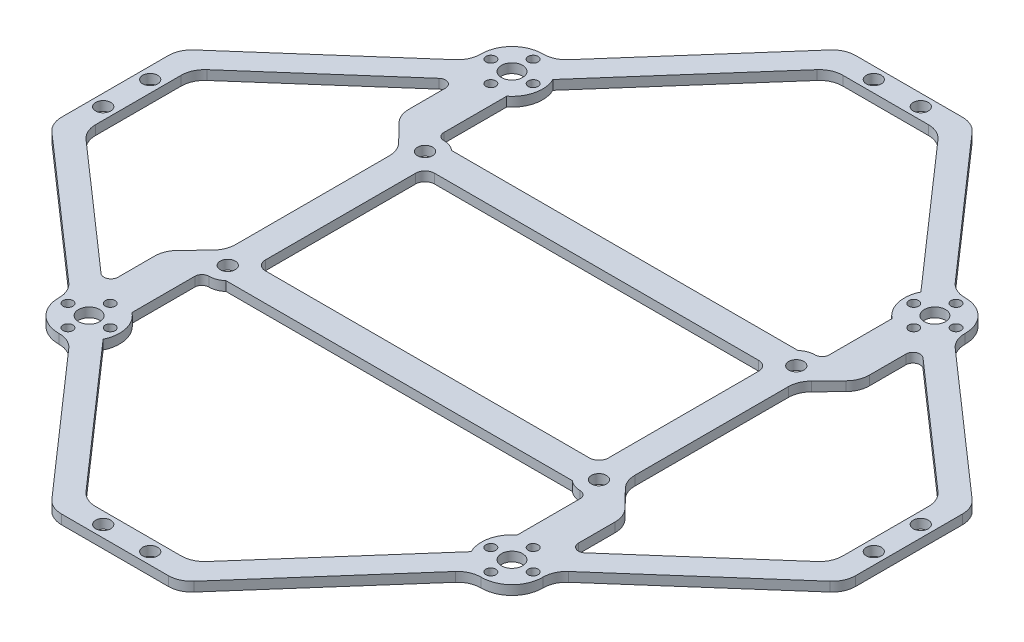
SolidWorks part; units mm, degrees
ref_plane "前视基准面" through (0, 0, 0) normal (0, 0, 1) x (1, 0, 0)
ref_plane "上视基准面" through (0, 0, 0) normal (0, 1, 0) x (1, 0, 0)
ref_plane "右视基准面" through (0, 0, 0) normal (1, 0, 0) x (0, 0, -1)
other "Configuration Table"
sketch "草图1" plane through (0, 0, 0) normal (0, 1, 0) x (1, 0, 0)
  line L0 (49, -45) -> (49, -39.8765) construction
  line L1 (-45, -45) -> (45, -45) construction
  line L2 (-45, -45) -> (-45, 45) construction
  line L3 (-45, 45) -> (45, 45) construction
  line L4 (45, -45) -> (45, 45) construction
  line L5 (-45, -45) -> (45, 45) construction
  line L6 (-45, 45) -> (45, -45) construction
  line L7 (-43.5, -25) -> (43.5, -25) construction
  line L8 (-43.5, -25) -> (-43.5, 25) construction
  line L9 (-43.5, 25) -> (43.5, 25) construction
  line L10 (43.5, -25) -> (43.5, 25) construction
  line L11 (-43.5, -25) -> (43.5, 25) construction
  line L12 (-43.5, 25) -> (43.5, -25) construction
  line L13 (-10, -10) -> (10, -10) construction
  line L14 (-10, -10) -> (-10, 10) construction
  line L15 (-10, 10) -> (10, 10) construction
  line L16 (10, -10) -> (10, 10) construction
  line L17 (-10, -10) -> (10, 10) construction
  line L18 (-10, 10) -> (10, -10) construction
  line L19 (41, -45) -> (41, 45) construction
  line L20 (41, 39.8765) -> (41, 26.5)
  line L21 (43.9235, 19.8039) -> (47.5765, 23.5429)
  line L22 (49, 34.8449) -> (49, 27.037)
  line L23 (0, 0) -> (14.7512, 0) construction
  line L24 (41, -26.5) -> (41, -39.8765)
  line L25 (49, -34.8449) -> (49, -27.037)
  line L26 (47.5765, -23.5429) -> (43.9235, -19.8039)
  line L27 (0, 0) -> (0, 21.9355) construction
  line L28 (-49, -45) -> (-49, -39.8765) construction
  line L29 (-41, -45) -> (-41, 45) construction
  line L30 (-45, -45) -> (-45, 45) construction
  line L31 (-41, -26.5) -> (-41, -39.8765)
  line L32 (-49, -34.8449) -> (-49, -27.037)
  line L33 (-47.5765, -23.5429) -> (-43.9235, -19.8039)
  line L34 (-49, 34.8449) -> (-49, 27.037)
  line L35 (-47.5765, 23.5429) -> (-43.9235, 19.8039)
  line L36 (-41, 39.8765) -> (-41, 26.5)
  line L37 (-39.5, 21) -> (39.5, 21) construction
  line L38 (39.5, 21) -> (39.5, -21) construction
  line L39 (-39.5, 21) -> (-39.5, -21) construction
  line L40 (-39.5, -21) -> (39.5, -21) construction
  line L42 (42.5, 16.3098) -> (42.5, -16.3098)
  line L44 (-42.5, 16.3098) -> (-42.5, -16.3098)
  line L45 (-34.5, -18) -> (34.5, -18)
  line L46 (36.5, 16) -> (36.5, -16)
  line L47 (-34.5, 18) -> (34.5, 18)
  line L48 (-36.5, 16) -> (-36.5, -16)
  line L49 (-42.5, 24) -> (-42.5, -24) construction
  line L50 (-36.8542, 24) -> (36.8542, 24)
  line L51 (-42.5, 24) -> (42.5, 24) construction
  line L52 (42.5, 24) -> (42.5, -24) construction
  line L53 (-36.8542, -24) -> (36.8542, -24)
  line L54 (-42.5, -24) -> (42.5, -24) construction
  line L55 (-45, 45) -> (-12.5, 82) construction
  line L56 (-12.5, 82) -> (12.5, 82) construction
  line L57 (12.5, 82) -> (45, 45) construction
  line L58 (-39.1621, 47.8581) -> (-12.862, 77.7997)
  line L59 (-9.1054, 79.5) -> (9.1054, 79.5)
  line L60 (12.862, 77.7997) -> (39.1621, 47.8581)
  line L61 (-41.1251, 53.1997) -> (-15.125, 82.7997)
  line L62 (-11.3685, 84.5) -> (11.3685, 84.5)
  line L63 (15.125, 82.7997) -> (41.1251, 53.1997)
  line L64 (82, 12.5) -> (82, -12.5) construction
  line L65 (45, 45) -> (82, 12.5) construction
  line L66 (82, -12.5) -> (45, -45) construction
  line L67 (12.5, -82) -> (-12.5, -82) construction
  line L68 (45, -45) -> (12.5, -82) construction
  line L69 (-12.5, -82) -> (-45, -45) construction
  line L70 (-82, -12.5) -> (-82, 12.5) construction
  line L71 (-45, -45) -> (-82, -12.5) construction
  line L72 (-82, 12.5) -> (-45, 45) construction
  line L73 (-46.8783, 46.6499) -> (-13.6315, 84.5) construction
  line L74 (-43.1217, 43.3501) -> (-11.3685, 79.5) construction
  line L75 (11.3685, 79.5) -> (43.1217, 43.3501) construction
  line L76 (-13.6315, -84.5) -> (-46.8783, -46.6499) construction
  line L77 (13.6315, 84.5) -> (46.8783, 46.6499) construction
  line L78 (-79.5, -9.1054) -> (-79.5, 9.1054)
  line L79 (-77.7997, 12.862) -> (-51.4899, 35.9719)
  line L80 (84.5, -13.6315) -> (46.6499, -46.8783) construction
  line L81 (9.1054, -79.5) -> (-9.1054, -79.5)
  line L82 (-12.862, -77.7997) -> (-39.1621, -47.8581)
  line L83 (51.4899, 35.9719) -> (77.7997, 12.862)
  line L84 (79.5, 9.1054) -> (79.5, -9.1054)
  line L85 (77.7997, -12.862) -> (51.4899, -35.9719)
  line L86 (-49, -38.159) -> (-49, 38.159) construction
  line L87 (-84.5, -11.3685) -> (-84.5, 11.3685)
  line L88 (-82.7997, 15.125) -> (-53.1997, 41.1251)
  line L89 (79.5, -11.3685) -> (43.3501, -43.1217) construction
  line L90 (11.3685, -84.5) -> (-11.3685, -84.5)
  line L91 (-15.125, -82.7997) -> (-41.1251, -53.1997)
  line L92 (43.3501, 43.1217) -> (79.5, 11.3685) construction
  line L93 (84.5, 11.3685) -> (84.5, -11.3685)
  line L94 (82.7997, -15.125) -> (53.1997, -41.1251)
  line L95 (-53.1997, -41.1251) -> (-82.7997, -15.125)
  line L96 (-84.5, 13.6315) -> (-46.6499, 46.8783) construction
  line L97 (-79.5, 11.3685) -> (-43.3501, 43.1217) construction
  line L98 (-46.6499, -46.8783) -> (-84.5, -13.6315) construction
  line L99 (-51.4899, -35.9719) -> (-77.7997, -12.862)
  line L100 (-43.3501, -43.1217) -> (-79.5, -11.3685) construction
  line L101 (-11.3685, -79.5) -> (-43.1217, -43.3501) construction
  line L102 (-49, 41.4865) -> (-49, 45) construction
  line L103 (39.1621, -47.8581) -> (12.862, -77.7997)
  line L104 (43.1217, -43.3501) -> (11.3685, -79.5) construction
  line L105 (46.8783, -46.6499) -> (13.6315, -84.5) construction
  line L106 (41.1251, -53.1997) -> (15.125, -82.7997)
  line L107 (49, -38.159) -> (49, 38.159) construction
  line L108 (49, -45) -> (49, 45) construction
  line L109 (49, 39.8765) -> (49, 45) construction
  line L110 (53.1997, 41.1251) -> (82.7997, 15.125)
  line L111 (46.6499, 46.8783) -> (84.5, 13.6315) construction
  line L112 (79.5, 11.3685) -> (79.5, -11.3685) construction
  line L113 (84.5, 13.6315) -> (84.5, -13.6315) construction
  line L114 (13.6315, -84.5) -> (-13.6315, -84.5) construction
  line L115 (11.3685, -79.5) -> (-11.3685, -79.5) construction
  line L116 (-79.5, -11.3685) -> (-79.5, 11.3685) construction
  line L117 (-84.5, -13.6315) -> (-84.5, 13.6315) construction
  line L118 (-13.6315, 84.5) -> (13.6315, 84.5) construction
  line L119 (-11.3685, 79.5) -> (11.3685, 79.5) construction
  line L120 (36.5, 18) -> (36.5, -18) construction
  line L121 (-36.5, 18) -> (36.5, 18) construction
  line L122 (-36.5, -18) -> (36.5, -18) construction
  line L123 (-36.5, 18) -> (-36.5, -18) construction
  circle A0 centre (45, 45) radius 31.5 construction
  circle A1 centre (-45, 45) radius 31.5 construction
  circle A2 centre (-45, -45) radius 31.5 construction
  circle A3 centre (45, -45) radius 31.5 construction
  circle A4 centre (-45, 45) radius 9.5 construction
  circle A5 centre (45, 45) radius 9.5 construction
  circle A6 centre (45, -45) radius 9.5 construction
  circle A7 centre (-45, -45) radius 9.5 construction
  circle A8 centre (-39.5, 21) radius 1.6
  circle A9 centre (39.5, 21) radius 1.6
  circle A10 centre (39.5, -21) radius 1.6
  circle A11 centre (-39.5, -21) radius 1.6
  circle A12 centre (-10, 10) radius 1.6 construction
  circle A13 centre (10, 10) radius 1.6 construction
  circle A14 centre (-10, -10) radius 1.6 construction
  circle A15 centre (10, -10) radius 1.6 construction
  arc A16 (51.4997, 44.9331) -> (44.9331, 51.4997) centre (45, 45) ccw
  arc A17 (-41, 39.8765) -> (-39.1621, 47.8581) centre (-45, 45) ccw
  arc A19 (41, -39.8765) -> (39.1621, -47.8581) centre (45, -45) ccw
  arc A20 (39.5, 25) -> (36.8542, 24) centre (39.5, 21) ccw
  arc A22 (41, 26.5) -> (39.5, 25) centre (39.5, 26.5) cw
  arc A23 (41, -26.5) -> (39.5, -25) centre (39.5, -26.5) ccw
  arc A24 (-36.8542, 24) -> (-39.5, 25) centre (-39.5, 21) ccw
  arc A25 (-39.5, -25) -> (-36.8542, -24) centre (-39.5, -21) ccw
  arc A26 (-41, -26.5) -> (-39.5, -25) centre (-39.5, -26.5) cw
  arc A27 (-41, 26.5) -> (-39.5, 25) centre (-39.5, 26.5) ccw
  arc A28 (-49, -27.037) -> (-47.5765, -23.5429) centre (-44, -27.037) cw
  arc A29 (36.8542, -24) -> (39.5, -25) centre (39.5, -21) ccw
  arc A30 (49, -27.037) -> (47.5765, -23.5429) centre (44, -27.037) ccw
  arc A31 (47.5765, 23.5429) -> (49, 27.037) centre (44, 27.037) ccw
  arc A32 (-49, 27.037) -> (-47.5765, 23.5429) centre (-44, 27.037) ccw
  arc A33 (43.9235, -19.8039) -> (42.5, -16.3098) centre (47.5, -16.3098) cw
  arc A34 (43.9235, 19.8039) -> (42.5, 16.3098) centre (47.5, 16.3098) ccw
  arc A35 (-42.5, -16.3098) -> (-43.9235, -19.8039) centre (-47.5, -16.3098) cw
  arc A36 (-42.5, 16.3098) -> (-43.9235, 19.8039) centre (-47.5, 16.3098) ccw
  circle A37 centre (45, 45) radius 2.25
  circle A38 centre (45, 49.5) radius 1.05
  circle A39 centre (49.5, 45) radius 1.05
  circle A40 centre (45, 40.5) radius 1.05
  circle A41 centre (40.5, 45) radius 1.05
  circle A42 centre (40.5, -45) radius 1.05
  circle A43 centre (45, -40.5) radius 1.05
  circle A44 centre (49.5, -45) radius 1.05
  circle A45 centre (45, -49.5) radius 1.05
  circle A46 centre (45, -45) radius 2.25
  circle A47 centre (-45, -40.5) radius 1.05
  circle A48 centre (-40.5, -45) radius 1.05
  circle A49 centre (-45, -49.5) radius 1.05
  circle A50 centre (-49.5, -45) radius 1.05
  circle A51 centre (-45, -45) radius 2.25
  circle A52 centre (-40.5, 45) radius 1.05
  circle A53 centre (-45, 40.5) radius 1.05
  circle A54 centre (-49.5, 45) radius 1.05
  circle A55 centre (-45, 49.5) radius 1.05
  circle A56 centre (-45, 45) radius 2.25
  arc A57 (-44.9331, 51.4997) -> (-51.4997, 44.9331) centre (-45, 45) ccw
  arc A58 (39.1621, 47.8581) -> (41, 39.8765) centre (45, 45) ccw
  arc A59 (-39.1621, -47.8581) -> (-41, -39.8765) centre (-45, -45) ccw
  arc A60 (-51.4997, -44.9331) -> (-44.9331, -51.4997) centre (-45, -45) ccw
  arc A61 (44.9331, -51.4997) -> (51.4997, -44.9331) centre (45, -45) ccw
  circle A62 centre (5, 82) radius 1.6
  circle A63 centre (-5, 82) radius 1.6
  circle A64 centre (82, 5) radius 1.6
  circle A65 centre (82, -5) radius 1.6
  circle A66 centre (5, -82) radius 1.6
  circle A67 centre (-5, -82) radius 1.6
  circle A68 centre (-82, -5) radius 1.6
  circle A69 centre (-82, 5) radius 1.6
  arc A70 (77.7997, 12.862) -> (79.5, 9.1054) centre (74.5, 9.1054) cw
  arc A71 (82.7997, 15.125) -> (84.5, 11.3685) centre (79.5, 11.3685) cw
  arc A72 (84.5, -11.3685) -> (82.7997, -15.125) centre (79.5, -11.3685) cw
  arc A73 (79.5, -9.1054) -> (77.7997, -12.862) centre (74.5, -9.1054) cw
  arc A74 (15.125, -82.7997) -> (11.3685, -84.5) centre (11.3685, -79.5) cw
  arc A75 (12.862, -77.7997) -> (9.1054, -79.5) centre (9.1054, -74.5) cw
  arc A76 (-11.3685, -84.5) -> (-15.125, -82.7997) centre (-11.3685, -79.5) cw
  arc A77 (-9.1054, -79.5) -> (-12.862, -77.7997) centre (-9.1054, -74.5) cw
  arc A78 (-77.7997, -12.862) -> (-79.5, -9.1054) centre (-74.5, -9.1054) cw
  arc A79 (-82.7997, -15.125) -> (-84.5, -11.3685) centre (-79.5, -11.3685) cw
  arc A80 (-79.5, 9.1054) -> (-77.7997, 12.862) centre (-74.5, 9.1054) cw
  arc A81 (-84.5, 11.3685) -> (-82.7997, 15.125) centre (-79.5, 11.3685) cw
  arc A82 (11.3685, 84.5) -> (15.125, 82.7997) centre (11.3685, 79.5) cw
  arc A83 (9.1054, 79.5) -> (12.862, 77.7997) centre (9.1054, 74.5) cw
  arc A84 (-12.862, 77.7997) -> (-9.1054, 79.5) centre (-9.1054, 74.5) cw
  arc A85 (-15.125, 82.7997) -> (-11.3685, 84.5) centre (-11.3685, 79.5) cw
  arc A86 (-53.1997, 41.1251) -> (-51.4997, 44.9331) centre (-56.4994, 44.8816) ccw
  arc A87 (-41.1251, 53.1997) -> (-44.9331, 51.4997) centre (-44.8816, 56.4994) cw
  arc A88 (41.1251, 53.1997) -> (44.9331, 51.4997) centre (44.8816, 56.4994) ccw
  arc A89 (51.4997, 44.9331) -> (53.1997, 41.1251) centre (56.4994, 44.8816) ccw
  arc A90 (53.1997, -41.1251) -> (51.4997, -44.9331) centre (56.4994, -44.8816) ccw
  arc A91 (44.9331, -51.4997) -> (41.1251, -53.1997) centre (44.8816, -56.4994) ccw
  arc A92 (-41.1251, -53.1997) -> (-44.9331, -51.4997) centre (-44.8816, -56.4994) ccw
  arc A93 (-53.1997, -41.1251) -> (-51.4997, -44.9331) centre (-56.4994, -44.8816) cw
  arc A94 (49, 34.8449) -> (51.4899, 35.9719) centre (50.5, 34.8449) cw
  arc A95 (51.4899, -35.9719) -> (49, -34.8449) centre (50.5, -34.8449) cw
  arc A96 (-51.4899, -35.9719) -> (-49, -34.8449) centre (-50.5, -34.8449) ccw
  arc A97 (-51.4899, 35.9719) -> (-49, 34.8449) centre (-50.5, 34.8449) cw
  arc A98 (36.5, 16) -> (34.5, 18) centre (34.5, 16) ccw
  arc A99 (34.5, -18) -> (36.5, -16) centre (34.5, -16) ccw
  arc A100 (-34.5, -18) -> (-36.5, -16) centre (-34.5, -16) cw
  arc A101 (-34.5, 18) -> (-36.5, 16) centre (-34.5, 16) ccw
  point P0 (0, 0)
  point P19 (0, 0)
  point P32 (0, 0)
  point P104 (-49, -25)
  point P107 (49, -25)
  point P110 (49, 25)
  point P113 (-49, 25)
  point P125 (45, 45)
  point P156 (0, 0)
  point P178 (0, 0)
  point P220 (0, 23.5429)
  point P236 (0, 0)
  point P288 (-42.9186, 51.1578)
  dimension "D3" = 63
  dimension "D4" = 63
  dimension "D5" = 63
  dimension "D6" = 63
  dimension "D7" = 19
  dimension "D8" = 19
  dimension "D9" = 19
  dimension "D10" = 19
  dimension "D15" = 3.2
  dimension "D18" = 3.2
  dimension "D21" = 3.2
  dimension "D24" = 3.2
  dimension "D27" = 3.2
  dimension "D28" = 3.2
  dimension "D29" = 3.2
  dimension "D30" = 3.2
  dimension "D31" = 13
  dimension "D32" = 13
  dimension "D33" = 3.2
  dimension "D34" = 13
  dimension "D35" = 8
  dimension "D36" = 3
  dimension "D17" = 8
  dimension "D23" = 8
  dimension "D39" = 5
  dimension "D40" = 5
  dimension "D41" = 4.5
  dimension "D42" = 2.1
  dimension "D44" = 4
  dimension "D54" = 3.2
  dimension "D58" = 5
  dimension "D59" = 5
  dimension "D60" = 1.5
  dimension "D61" = 2
  dimension "D1" = 90
  dimension "D2" = 90
  dimension "D11" = 87
  dimension "D12" = 50
  dimension "D13" = 3
  dimension "D14" = 4
  dimension "D16" = 4
  dimension "D19" = 3
  dimension "D20" = 4
  dimension "D22" = 4
  dimension "D25" = 20
  dimension "D26" = 20
  dimension "D43" = 4.5
  dimension "D46" = 25
  dimension "D47" = 12.5
  dimension "D50" = 82
  dimension "D55" = 5
  dimension "D56" = 5
  dimension "D37" = 4
  dimension "D38" = 4
  dimension "D48" = 2.5
  dimension "D49" = 2.5
  dimension "D52" = 2.5
  dimension "D53" = 2.5
  dimension "D45" = 4
  dimension "D51" = 4
  dimension "D57" = 4
extrude "凸台-拉伸2" add sketch "草图1" along normal blind 2
